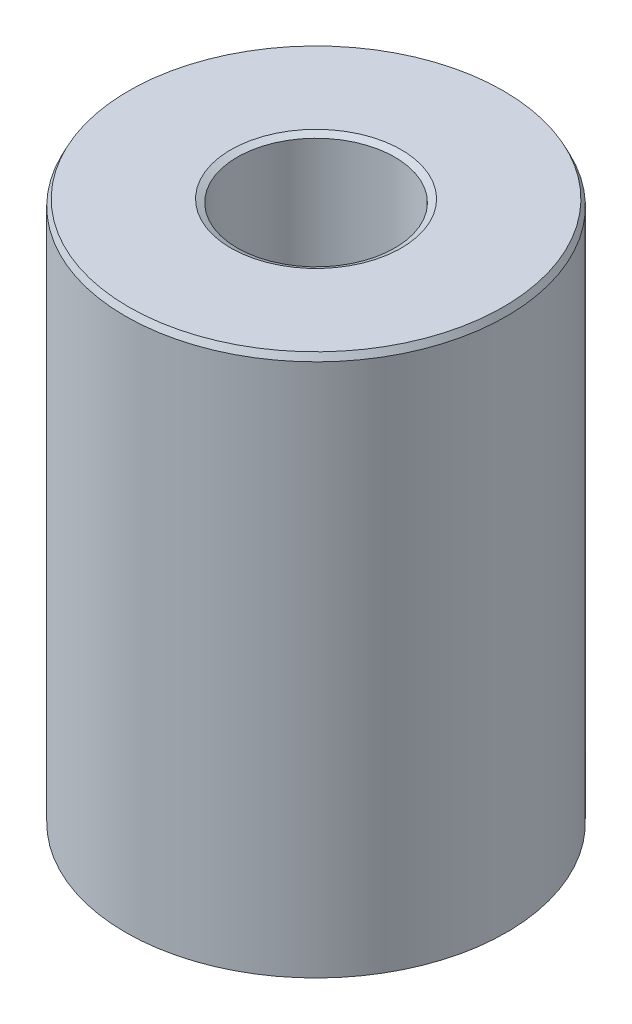
SolidWorks part; units mm, degrees
ref_plane "Front Plane" through (0, 0, 0) normal (0, 0, 1) x (1, 0, 0)
ref_plane "Top Plane" through (0, 0, 0) normal (0, 1, 0) x (1, 0, 0)
ref_plane "Right Plane" through (0, 0, 0) normal (1, 0, 0) x (0, 0, -1)
sketch "Sketch1" plane through (0, 0, 0) normal (0, 1, 0) x (1, 0, 0)
  circle A0 centre (0, 0) radius 35
  dimension "SLEEVE_OD" = 70
extrude "Boss-Extrude1" add sketch "Sketch1" along normal blind 99.8299
sketch "Sketch2" plane through (0, 0, 0) normal (0, 1, 0) x (1, 0, 0)
  circle A0 centre (0, 0) radius 14.4771
  dimension "BORE_D" = 28.9543
extrude "Cut-Extrude1" cut sketch "Sketch2" along normal through all
chamfer "Chamfer1" distance 1.1881 angle 26.049 4 edges at (0, 99.8299, 14.4771) (0, 0, 14.4771) (0, 0, 35) (0, 99.8299, 35) first distance on face at (0, 99.8299, 14.4771) first distance on face at (0, 0, 14.4771) first distance on face at (0, 99.8299, 35)
